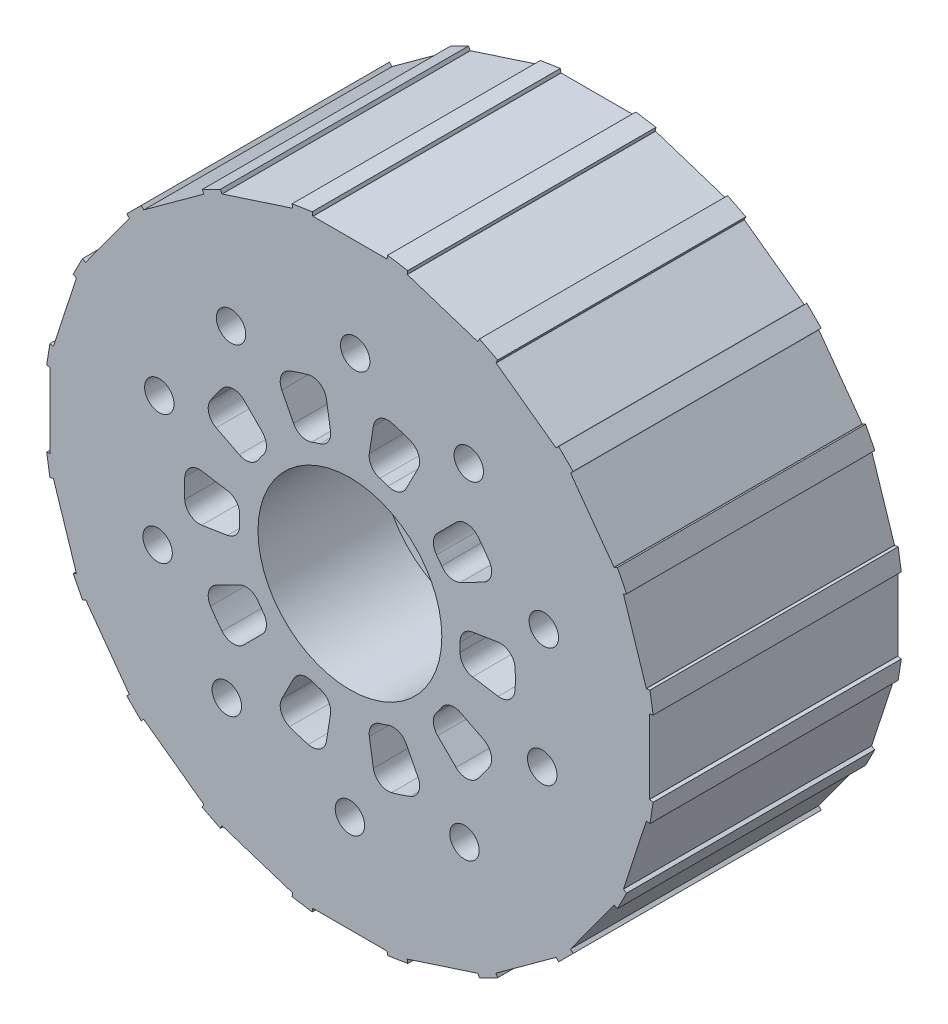
SolidWorks part; units mm, degrees
ref_plane "Ön Düzlem" through (0, 0, 0) normal (0, 0, 1) x (1, 0, 0)
ref_plane "Üst Düzlem" through (0, 0, 0) normal (0, 1, 0) x (1, 0, 0)
ref_plane "Sağ Düzlem" through (0, 0, 0) normal (1, 0, 0) x (0, 0, -1)
sketch "Sketch1" plane through (0, 0, 0) normal (0, 0, 1) x (1, 0, 0)
  line L0 (0, 0) -> (0, 81.5)
  line L1 (10, 81.5) -> (-10, 81.5)
  line L2 (-10, 81.5) -> (-10, 87.5)
  line L3 (10, 81.5) -> (10, 87.5)
  line L4 (15.6743, 80.6013) -> (17.5284, 86.3076)
  line L5 (34.6955, 74.4209) -> (36.5496, 80.1273)
  line L6 (34.6955, 74.4209) -> (15.6743, 80.6013)
  line L7 (39.8143, 71.8127) -> (43.341, 76.6668)
  line L8 (55.9947, 60.057) -> (59.5214, 64.9111)
  line L9 (55.9947, 60.057) -> (39.8143, 71.8127)
  line L10 (60.057, 55.9947) -> (64.9111, 59.5214)
  line L11 (71.8127, 39.8143) -> (76.6668, 43.341)
  line L12 (71.8127, 39.8143) -> (60.057, 55.9947)
  line L13 (74.4209, 34.6955) -> (80.1273, 36.5496)
  line L14 (80.6013, 15.6743) -> (86.3076, 17.5284)
  line L15 (80.6013, 15.6743) -> (74.4209, 34.6955)
  line L16 (81.5, 10) -> (87.5, 10)
  line L17 (81.5, -10) -> (87.5, -10)
  line L18 (81.5, -10) -> (81.5, 10)
  line L19 (80.6013, -15.6743) -> (86.3076, -17.5284)
  line L20 (74.4209, -34.6955) -> (80.1273, -36.5496)
  line L21 (74.4209, -34.6955) -> (80.6013, -15.6743)
  line L22 (71.8127, -39.8143) -> (76.6668, -43.341)
  line L23 (60.057, -55.9947) -> (64.9111, -59.5214)
  line L24 (60.057, -55.9947) -> (71.8127, -39.8143)
  line L25 (55.9947, -60.057) -> (59.5214, -64.9111)
  line L26 (39.8143, -71.8127) -> (43.341, -76.6668)
  line L27 (39.8143, -71.8127) -> (55.9947, -60.057)
  line L28 (34.6955, -74.4209) -> (36.5496, -80.1273)
  line L29 (15.6743, -80.6013) -> (17.5284, -86.3076)
  line L30 (15.6743, -80.6013) -> (34.6955, -74.4209)
  line L31 (10, -81.5) -> (10, -87.5)
  line L32 (-10, -81.5) -> (-10, -87.5)
  line L33 (-10, -81.5) -> (10, -81.5)
  line L34 (-15.6743, -80.6013) -> (-17.5284, -86.3076)
  line L35 (-34.6955, -74.4209) -> (-36.5496, -80.1273)
  line L36 (-34.6955, -74.4209) -> (-15.6743, -80.6013)
  line L37 (-39.8143, -71.8127) -> (-43.341, -76.6668)
  line L38 (-55.9947, -60.057) -> (-59.5214, -64.9111)
  line L39 (-55.9947, -60.057) -> (-39.8143, -71.8127)
  line L40 (-60.057, -55.9947) -> (-64.9111, -59.5214)
  line L41 (-71.8127, -39.8143) -> (-76.6668, -43.341)
  line L42 (-71.8127, -39.8143) -> (-60.057, -55.9947)
  line L43 (-74.4209, -34.6955) -> (-80.1273, -36.5496)
  line L44 (-80.6013, -15.6743) -> (-86.3076, -17.5284)
  line L45 (-80.6013, -15.6743) -> (-74.4209, -34.6955)
  line L46 (-81.5, -10) -> (-87.5, -10)
  line L47 (-81.5, 10) -> (-87.5, 10)
  line L48 (-81.5, 10) -> (-81.5, -10)
  line L49 (-80.6013, 15.6743) -> (-86.3076, 17.5284)
  line L50 (-74.4209, 34.6955) -> (-80.1273, 36.5496)
  line L51 (-74.4209, 34.6955) -> (-80.6013, 15.6743)
  line L52 (-71.8127, 39.8143) -> (-76.6668, 43.341)
  line L53 (-60.057, 55.9947) -> (-64.9111, 59.5214)
  line L54 (-60.057, 55.9947) -> (-71.8127, 39.8143)
  line L55 (-55.9947, 60.057) -> (-59.5214, 64.9111)
  line L56 (-39.8143, 71.8127) -> (-43.341, 76.6668)
  line L57 (-39.8143, 71.8127) -> (-55.9947, 60.057)
  line L58 (-34.6955, 74.4209) -> (-36.5496, 80.1273)
  line L59 (-15.6743, 80.6013) -> (-17.5284, 86.3076)
  line L60 (-15.6743, 80.6013) -> (-34.6955, 74.4209)
  line L61 (34.6955, 74.4209) -> (34.7846, 74.3755)
  line L62 (35.1494, 75.3119) -> (40.2683, 72.7037) construction
  line L63 (39.7252, 71.8581) -> (39.8143, 71.8127)
  line L64 (35.2385, 75.2665) -> (40.1792, 72.7491)
  line L65 (34.7846, 74.3755) -> (35.2385, 75.2665)
  line L66 (55.9947, 60.057) -> (56.0654, 59.9863)
  line L67 (39.7252, 71.8581) -> (40.1792, 72.7491)
  line L68 (34.7846, 74.3755) -> (35.1931, 75.1774) construction
  line L69 (39.7252, 71.8581) -> (40.1338, 72.66) construction
  line L70 (35.1931, 75.1774) -> (40.1338, 72.66) construction
  line L71 (34.6955, 74.4209) -> (35.1494, 75.3119) construction
  line L72 (39.8143, 71.8127) -> (40.2683, 72.7037) construction
  line L73 (56.0654, 59.9863) -> (56.7725, 60.6934)
  line L74 (56.7725, 60.6934) -> (60.6934, 56.7725)
  line L75 (59.9863, 56.0654) -> (60.6934, 56.7725)
  line L76 (59.9863, 56.0654) -> (60.057, 55.9947)
  line L77 (71.8127, 39.8143) -> (71.8581, 39.7252)
  line L78 (71.8581, 39.7252) -> (72.7491, 40.1792)
  line L79 (72.7491, 40.1792) -> (75.2665, 35.2385)
  line L80 (74.3755, 34.7846) -> (75.2665, 35.2385)
  line L81 (74.3755, 34.7846) -> (74.4209, 34.6955)
  line L82 (80.6013, 15.6743) -> (80.6169, 15.5756)
  line L83 (80.6169, 15.5756) -> (81.6046, 15.732)
  line L84 (81.6046, 15.732) -> (82.472, 10.2552)
  line L85 (81.4844, 10.0988) -> (82.472, 10.2552)
  line L86 (81.4844, 10.0988) -> (81.5, 10)
  line L87 (81.5, -10) -> (81.4844, -10.0988)
  line L88 (81.4844, -10.0988) -> (82.472, -10.2552)
  line L89 (82.472, -10.2552) -> (81.6046, -15.732)
  line L90 (80.6169, -15.5756) -> (81.6046, -15.732)
  line L91 (80.6169, -15.5756) -> (80.6013, -15.6743)
  line L92 (74.4209, -34.6955) -> (74.3755, -34.7846)
  line L93 (74.3755, -34.7846) -> (75.2665, -35.2385)
  line L94 (75.2665, -35.2385) -> (72.7491, -40.1792)
  line L95 (71.8581, -39.7252) -> (72.7491, -40.1792)
  line L96 (71.8581, -39.7252) -> (71.8127, -39.8143)
  line L97 (60.057, -55.9947) -> (59.9863, -56.0654)
  line L98 (59.9863, -56.0654) -> (60.6934, -56.7725)
  line L99 (60.6934, -56.7725) -> (56.7725, -60.6934)
  line L100 (56.0654, -59.9863) -> (56.7725, -60.6934)
  line L101 (56.0654, -59.9863) -> (55.9947, -60.057)
  line L102 (39.8143, -71.8127) -> (39.7252, -71.8581)
  line L103 (39.7252, -71.8581) -> (40.1792, -72.7491)
  line L104 (40.1792, -72.7491) -> (35.2385, -75.2665)
  line L105 (34.7846, -74.3755) -> (35.2385, -75.2665)
  line L106 (34.7846, -74.3755) -> (34.6955, -74.4209)
  line L107 (15.6743, -80.6013) -> (15.5756, -80.6169)
  line L108 (15.5756, -80.6169) -> (15.732, -81.6046)
  line L109 (15.732, -81.6046) -> (10.2552, -82.472)
  line L110 (10.0988, -81.4844) -> (10.2552, -82.472)
  line L111 (10.0988, -81.4844) -> (10, -81.5)
  line L112 (-10, -81.5) -> (-10.0988, -81.4844)
  line L113 (-10.0988, -81.4844) -> (-10.2552, -82.472)
  line L114 (-10.2552, -82.472) -> (-15.732, -81.6046)
  line L115 (-15.5756, -80.6169) -> (-15.732, -81.6046)
  line L116 (-15.5756, -80.6169) -> (-15.6743, -80.6013)
  line L117 (-34.6955, -74.4209) -> (-34.7846, -74.3755)
  line L118 (-34.7846, -74.3755) -> (-35.2385, -75.2665)
  line L119 (-35.2385, -75.2665) -> (-40.1792, -72.7491)
  line L120 (-39.7252, -71.8581) -> (-40.1792, -72.7491)
  line L121 (-39.7252, -71.8581) -> (-39.8143, -71.8127)
  line L122 (-55.9947, -60.057) -> (-56.0654, -59.9863)
  line L123 (-56.0654, -59.9863) -> (-56.7725, -60.6934)
  line L124 (-56.7725, -60.6934) -> (-60.6934, -56.7725)
  line L125 (-59.9863, -56.0654) -> (-60.6934, -56.7725)
  line L126 (-59.9863, -56.0654) -> (-60.057, -55.9947)
  line L127 (-71.8127, -39.8143) -> (-71.8581, -39.7252)
  line L128 (-71.8581, -39.7252) -> (-72.7491, -40.1792)
  line L129 (-72.7491, -40.1792) -> (-75.2665, -35.2385)
  line L130 (-74.3755, -34.7846) -> (-75.2665, -35.2385)
  line L131 (-74.3755, -34.7846) -> (-74.4209, -34.6955)
  line L132 (-80.6013, -15.6743) -> (-80.6169, -15.5756)
  line L133 (-80.6169, -15.5756) -> (-81.6046, -15.732)
  line L134 (-81.6046, -15.732) -> (-82.472, -10.2552)
  line L135 (-81.4844, -10.0988) -> (-82.472, -10.2552)
  line L136 (-81.4844, -10.0988) -> (-81.5, -10)
  line L137 (-81.5, 10) -> (-81.4844, 10.0988)
  line L138 (-81.4844, 10.0988) -> (-82.472, 10.2552)
  line L139 (-82.472, 10.2552) -> (-81.6046, 15.732)
  line L140 (-80.6169, 15.5756) -> (-81.6046, 15.732)
  line L141 (-80.6169, 15.5756) -> (-80.6013, 15.6743)
  line L142 (-74.4209, 34.6955) -> (-74.3755, 34.7846)
  line L143 (-74.3755, 34.7846) -> (-75.2665, 35.2385)
  line L144 (-75.2665, 35.2385) -> (-72.7491, 40.1792)
  line L145 (-71.8581, 39.7252) -> (-72.7491, 40.1792)
  line L146 (-71.8581, 39.7252) -> (-71.8127, 39.8143)
  line L147 (-60.057, 55.9947) -> (-59.9863, 56.0654)
  line L148 (-59.9863, 56.0654) -> (-60.6934, 56.7725)
  line L149 (-60.6934, 56.7725) -> (-56.7725, 60.6934)
  line L150 (-56.0654, 59.9863) -> (-56.7725, 60.6934)
  line L151 (-56.0654, 59.9863) -> (-55.9947, 60.057)
  line L152 (-39.8143, 71.8127) -> (-39.7252, 71.8581)
  line L153 (-39.7252, 71.8581) -> (-40.1792, 72.7491)
  line L154 (-40.1792, 72.7491) -> (-35.2385, 75.2665)
  line L155 (-34.7846, 74.3755) -> (-35.2385, 75.2665)
  line L156 (-34.7846, 74.3755) -> (-34.6955, 74.4209)
  line L157 (-15.6743, 80.6013) -> (-15.5756, 80.6169)
  line L158 (-15.5756, 80.6169) -> (-15.732, 81.6046)
  line L159 (-15.732, 81.6046) -> (-10.2552, 82.472)
  line L160 (-10.0988, 81.4844) -> (-10.2552, 82.472)
  line L161 (-10.0988, 81.4844) -> (-10, 81.5)
  line L162 (10, 81.5) -> (10.0988, 81.4844)
  line L163 (10.0988, 81.4844) -> (10.2552, 82.472)
  line L164 (10.2552, 82.472) -> (15.732, 81.6046)
  line L165 (15.5756, 80.6169) -> (15.732, 81.6046)
  line L166 (15.5756, 80.6169) -> (15.6743, 80.6013)
  circle A0 centre (0, 0) radius 25
  arc A2 (10, 87.5) -> (-10, 87.5) centre (0, 38) ccw
  arc A3 (36.5496, 80.1273) -> (17.5284, 86.3076) centre (11.7426, 36.1401) ccw
  arc A4 (59.5214, 64.9111) -> (43.341, 76.6668) centre (22.3358, 30.7426) ccw
  arc A5 (76.6668, 43.341) -> (64.9111, 59.5214) centre (30.7426, 22.3358) ccw
  arc A6 (86.3076, 17.5284) -> (80.1273, 36.5496) centre (36.1401, 11.7426) ccw
  arc A7 (87.5, -10) -> (87.5, 10) centre (38, 0) ccw
  arc A8 (80.1273, -36.5496) -> (86.3076, -17.5284) centre (36.1401, -11.7426) ccw
  arc A9 (64.9111, -59.5214) -> (76.6668, -43.341) centre (30.7426, -22.3358) ccw
  arc A10 (43.341, -76.6668) -> (59.5214, -64.9111) centre (22.3358, -30.7426) ccw
  arc A11 (17.5284, -86.3076) -> (36.5496, -80.1273) centre (11.7426, -36.1401) ccw
  arc A12 (-10, -87.5) -> (10, -87.5) centre (0, -38) ccw
  arc A13 (-36.5496, -80.1273) -> (-17.5284, -86.3076) centre (-11.7426, -36.1401) ccw
  arc A14 (-59.5214, -64.9111) -> (-43.341, -76.6668) centre (-22.3358, -30.7426) ccw
  arc A15 (-76.6668, -43.341) -> (-64.9111, -59.5214) centre (-30.7426, -22.3358) ccw
  arc A16 (-86.3076, -17.5284) -> (-80.1273, -36.5496) centre (-36.1401, -11.7426) ccw
  arc A17 (-87.5, 10) -> (-87.5, -10) centre (-38, 0) ccw
  arc A18 (-80.1273, 36.5496) -> (-86.3076, 17.5284) centre (-36.1401, 11.7426) ccw
  arc A19 (-64.9111, 59.5214) -> (-76.6668, 43.341) centre (-30.7426, 22.3358) ccw
  arc A20 (-43.341, 76.6668) -> (-59.5214, 64.9111) centre (-22.3358, 30.7426) ccw
  arc A21 (-17.5284, 86.3076) -> (-36.5496, 80.1273) centre (-11.7426, 36.1401) ccw
  point P7 (0, 81.5)
  point P107 (0, 0)
  point P231 (0, 0)
  dimension "D1" = 81.5
  dimension "D3" = 50.5
  dimension "D8" = 50
  dimension "D2" = 20
  dimension "D4" = 6
  dimension "D5" = 6
  dimension "D7" = 20
  dimension "D6" = 20
extrude "Boss-Extrude1" add sketch "Sketch1" along normal blind 67.5 contours A0 L1 L161 L160 L159 L158 L157 L60 L156 L155 L154 L153 L152 L57 L151 L150 L149 L148 L147 L54 L146 L145 L144 L143 L142 L51 L141 L140 L139 L138 L137 L48 L136 L135 L134 L133 L132 L45 L131 L130 L129 L128 L127 L42 L126 L125 L124 L123 L122 L39 region at (5, 79.1673, 0)
sketch "Sketch2" plane through (0, 0, 0) normal (0, 0, -1) x (-1, 0, 0)
  circle A0 centre (0, 0) radius 68
extrude "Cut-Extrude1" cut sketch "Sketch2" against normal blind 33.75
sketch "Sketch3" plane through (0, 0, 33.75) normal (0, 0, -1) x (-1, 0, 0)
  line L0 (0, 0) -> (0, 55)
  line L1 (0, 0) -> (1.4397, 54.9812)
  circle A1 centre (32.3282, 44.4959) radius 4
  circle A3 centre (52.3081, -16.9959) radius 4
  circle A5 centre (0, -55) radius 4
  circle A7 centre (-52.3081, -16.9959) radius 4
  circle A9 centre (-32.3282, 44.4959) radius 4
  circle A11 centre (1.4397, 54.9812) radius 4
  circle A12 centre (52.7351, 15.6208) radius 4
  circle A13 centre (31.1523, -45.3269) radius 4
  circle A14 centre (-33.4819, -43.6344) radius 4
  circle A15 centre (-51.8453, 18.3594) radius 4
  point P24 (0, 0)
  point P28 (0, 0)
  point P37 (0, 0)
extrude "Cut-Extrude2" cut sketch "Sketch3" against normal blind 33.75 contours A9 | A1 | A3 | A5 | A7
sketch "Sketch4" plane through (0, 0, 33.75) normal (0, 0, -1) x (-1, 0, 0)
  line L1 (-5.2818, 33.3482) -> (-6.3832, 40.302)
  line L2 (-15.3285, 30.0838) -> (-18.5248, 36.357)
  line L3 (15.3285, 30.0838) -> (18.5248, 36.357)
  line L4 (5.2818, 33.3482) -> (6.3832, 40.302)
  line L5 (30.0838, 15.3285) -> (36.357, 18.5248)
  line L6 (23.8747, 23.8747) -> (28.8531, 28.8531)
  line L7 (33.3482, -5.2818) -> (40.302, -6.3832)
  line L8 (33.3482, 5.2818) -> (40.302, 6.3832)
  line L9 (23.8747, -23.8747) -> (28.8531, -28.8531)
  line L10 (30.0838, -15.3285) -> (36.357, -18.5248)
  line L11 (5.2818, -33.3482) -> (6.3832, -40.302)
  line L12 (15.3285, -30.0838) -> (18.5248, -36.357)
  line L13 (-15.3285, -30.0838) -> (-18.5248, -36.357)
  line L14 (-5.2818, -33.3482) -> (-6.3832, -40.302)
  line L18 (-30.0838, 15.3285) -> (-36.357, 18.5248)
  line L19 (-23.8747, 23.8747) -> (-28.8531, 28.8531)
  line L24 (-30.0838, -15.3285) -> (-36.357, -18.5248)
  line L25 (-23.8747, -23.8747) -> (-28.8531, -28.8531)
  line L26 (-33.3482, 5.2818) -> (-40.302, 6.3832)
  line L27 (-33.3482, -5.2818) -> (-40.302, -6.3832)
  arc A0 (-34.7724, 28.5636) -> (-37.9109, 24.2439) centre (0, 0) ccw
  arc A1 (-23.5616, 18.5702) -> (-24.9422, 16.6699) centre (0, 0) ccw
  arc A6 (-37.9109, 24.2439) -> (-36.357, 18.5248) centre (-34.541, 22.0888) ccw
  arc A7 (-30.0838, 15.3285) -> (-24.9422, 16.6699) centre (-28.2679, 18.8925) ccw
  arc A8 (-23.5616, 18.5702) -> (-23.8747, 23.8747) centre (-26.7031, 21.0462) ccw
  arc A9 (-28.8531, 28.8531) -> (-34.7724, 28.5636) centre (-31.6815, 26.0246) ccw
  arc A10 (-6.3832, 40.302) -> (-11.3422, 43.5472) centre (-10.334, 39.6763) ccw
  arc A11 (-8.1464, 28.8728) -> (-5.2818, 33.3482) centre (-9.2326, 32.7225) ccw
  arc A12 (-11.3422, 43.5472) -> (-16.4204, 41.8971) centre (0, 0) ccw
  arc A13 (-16.4204, 41.8971) -> (-18.5248, 36.357) centre (-14.9608, 38.173) ccw
  arc A14 (-15.3285, 30.0838) -> (-10.3804, 28.1469) centre (-11.7645, 31.8998) ccw
  arc A15 (-8.1464, 28.8728) -> (-10.3804, 28.1469) centre (0, 0) ccw
  arc A16 (18.5248, 36.357) -> (16.4204, 41.8971) centre (14.9608, 38.173) ccw
  arc A17 (10.3804, 28.1469) -> (15.3285, 30.0838) centre (11.7645, 31.8998) ccw
  arc A18 (16.4204, 41.8971) -> (11.3422, 43.5472) centre (0, 0) ccw
  arc A19 (11.3422, 43.5472) -> (6.3832, 40.302) centre (10.334, 39.6763) ccw
  arc A20 (5.2818, 33.3482) -> (8.1464, 28.8728) centre (9.2326, 32.7225) ccw
  arc A21 (10.3804, 28.1469) -> (8.1464, 28.8728) centre (0, 0) ccw
  arc A22 (36.357, 18.5248) -> (37.9109, 24.2439) centre (34.541, 22.0888) ccw
  arc A23 (24.9422, 16.6699) -> (30.0838, 15.3285) centre (28.2679, 18.8925) ccw
  arc A24 (37.9109, 24.2439) -> (34.7724, 28.5636) centre (0, 0) ccw
  arc A25 (34.7724, 28.5636) -> (28.8531, 28.8531) centre (31.6815, 26.0246) ccw
  arc A26 (23.8747, 23.8747) -> (23.5616, 18.5702) centre (26.7031, 21.0462) ccw
  arc A27 (24.9422, 16.6699) -> (23.5616, 18.5702) centre (0, 0) ccw
  arc A28 (40.302, -6.3832) -> (44.9207, -2.6698) centre (40.9278, -2.4325) ccw
  arc A29 (29.977, -1.1745) -> (33.3482, -5.2818) centre (33.9739, -1.3311) ccw
  arc A30 (44.9207, -2.6698) -> (44.9207, 2.6698) centre (0, 0) ccw
  arc A31 (44.9207, 2.6698) -> (40.302, 6.3832) centre (40.9278, 2.4325) ccw
  arc A32 (33.3482, 5.2818) -> (29.977, 1.1745) centre (33.9739, 1.3311) ccw
  arc A33 (29.977, -1.1745) -> (29.977, 1.1745) centre (0, 0) ccw
  arc A34 (28.8531, -28.8531) -> (34.7724, -28.5636) centre (31.6815, -26.0246) ccw
  arc A35 (23.5616, -18.5702) -> (23.8747, -23.8747) centre (26.7031, -21.0462) ccw
  arc A36 (34.7724, -28.5636) -> (37.9109, -24.2439) centre (0, 0) ccw
  arc A37 (37.9109, -24.2439) -> (36.357, -18.5248) centre (34.541, -22.0888) ccw
  arc A38 (30.0838, -15.3285) -> (24.9422, -16.6699) centre (28.2679, -18.8925) ccw
  arc A39 (23.5616, -18.5702) -> (24.9422, -16.6699) centre (0, 0) ccw
  arc A40 (6.3832, -40.302) -> (11.3422, -43.5472) centre (10.334, -39.6763) ccw
  arc A41 (8.1464, -28.8728) -> (5.2818, -33.3482) centre (9.2326, -32.7225) ccw
  arc A42 (11.3422, -43.5472) -> (16.4204, -41.8971) centre (0, 0) ccw
  arc A43 (16.4204, -41.8971) -> (18.5248, -36.357) centre (14.9608, -38.173) ccw
  arc A44 (15.3285, -30.0838) -> (10.3804, -28.1469) centre (11.7645, -31.8998) ccw
  arc A45 (8.1464, -28.8728) -> (10.3804, -28.1469) centre (0, 0) ccw
  arc A46 (-18.5248, -36.357) -> (-16.4204, -41.8971) centre (-14.9608, -38.173) ccw
  arc A47 (-10.3804, -28.1469) -> (-15.3285, -30.0838) centre (-11.7645, -31.8998) ccw
  arc A48 (-16.4204, -41.8971) -> (-11.3422, -43.5472) centre (0, 0) ccw
  arc A49 (-11.3422, -43.5472) -> (-6.3832, -40.302) centre (-10.334, -39.6763) ccw
  arc A50 (-5.2818, -33.3482) -> (-8.1464, -28.8728) centre (-9.2326, -32.7225) ccw
  arc A51 (-10.3804, -28.1469) -> (-8.1464, -28.8728) centre (0, 0) ccw
  arc A52 (-36.357, -18.5248) -> (-37.9109, -24.2439) centre (-34.541, -22.0888) ccw
  arc A53 (-24.9422, -16.6699) -> (-30.0838, -15.3285) centre (-28.2679, -18.8925) ccw
  arc A54 (-37.9109, -24.2439) -> (-34.7724, -28.5636) centre (0, 0) ccw
  arc A55 (-34.7724, -28.5636) -> (-28.8531, -28.8531) centre (-31.6815, -26.0246) ccw
  arc A56 (-23.8747, -23.8747) -> (-23.5616, -18.5702) centre (-26.7031, -21.0462) ccw
  arc A57 (-24.9422, -16.6699) -> (-23.5616, -18.5702) centre (0, 0) ccw
  arc A58 (-40.302, 6.3832) -> (-44.9207, 2.6698) centre (-40.9278, 2.4325) ccw
  arc A59 (-29.977, 1.1745) -> (-33.3482, 5.2818) centre (-33.9739, 1.3311) ccw
  arc A60 (-44.9207, 2.6698) -> (-44.9207, -2.6698) centre (0, 0) ccw
  arc A61 (-44.9207, -2.6698) -> (-40.302, -6.3832) centre (-40.9278, -2.4325) ccw
  arc A62 (-33.3482, -5.2818) -> (-29.977, -1.1745) centre (-33.9739, -1.3311) ccw
  arc A63 (-29.977, 1.1745) -> (-29.977, -1.1745) centre (0, 0) ccw
  point P132 (0, 0)
  dimension "D1" = 4
extrude "Cut-Extrude3" cut sketch "Sketch4" against normal blind 33.75
sketch "Sketch5" plane through (0, 0, 33.75) normal (0, 0, -1) x (-1, 0, 0)
  line L0 (0, 0) -> (-1.4397, 54.9812)
  circle A0 centre (-1.4397, 54.9812) radius 4
  circle A1 centre (51.8453, 18.3594) radius 4
  circle A2 centre (33.4819, -43.6344) radius 4
  circle A3 centre (-31.1523, -45.3269) radius 4
  circle A4 centre (-52.7351, 15.6208) radius 4
  point P14 (0, 0)
extrude "Cut-Extrude4" cut sketch "Sketch5" against normal through all contours A4 | A0 | A1 | A2 | A3
